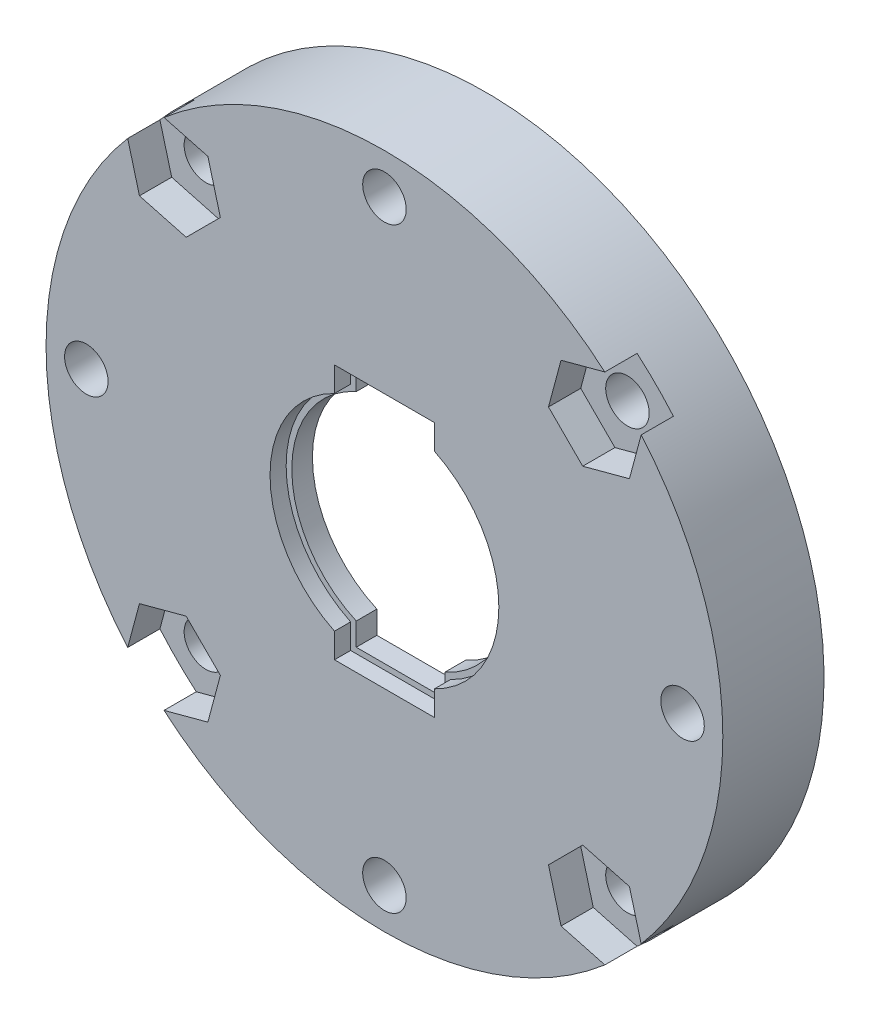
SolidWorks part; units mm, degrees
ref_plane "Front Plane" through (0, 0, 0) normal (0, 0, 1) x (1, 0, 0)
ref_plane "Top Plane" through (0, 0, 0) normal (0, 1, 0) x (1, 0, 0)
ref_plane "Right Plane" through (0, 0, 0) normal (1, 0, 0) x (0, 0, -1)
ref_axis "Z" through (0, 0, -0.1) along (0, 0, 1)
sketch "Sketch3" plane through (0, 0, 0) normal (0, 0, 1) x (1, 0, 0)
  line L0 (-3.1, -6.3875) -> (-3.1, -7.9247)
  line L1 (-3.1, -7.9247) -> (3.1, -7.9247)
  line L2 (3.1, -7.9247) -> (3.1, -6.3875)
  line L3 (3.1, 6.3875) -> (3.1, 7.9244)
  line L4 (3.1, 7.9244) -> (-3.1, 7.9244)
  line L5 (-3.1, 7.9244) -> (-3.1, 6.3875)
  line L132 (3.05, 6.3548) -> (3.05, 6.3561) construction
  line L133 (-3.05, 6.3561) -> (-3.05, 6.3548) construction
  line L134 (3.05, -6.3561) -> (3.05, -6.355) construction
  line L135 (-3.05, -6.355) -> (-3.05, -6.3561) construction
  line L198 (3.05, 6.3548) -> (3.05, 7.8744)
  line L199 (3.05, 7.8744) -> (-3.05, 7.8744)
  line L200 (-3.05, 7.8744) -> (-3.05, 6.3548)
  line L201 (-3.05, 6.3548) -> (-3.4914, 6.1247)
  line L202 (-3.4914, 6.1247) -> (-3.9416, 5.8451)
  line L203 (-3.9416, 5.8451) -> (-4.3696, 5.5325)
  line L204 (-4.3696, 5.5325) -> (-4.7729, 5.1886)
  line L205 (-4.7729, 5.1886) -> (-5.1492, 4.8154)
  line L206 (-5.1492, 4.8154) -> (-5.4964, 4.4149)
  line L207 (-5.4964, 4.4149) -> (-5.8125, 3.9896)
  line L208 (-5.8125, 3.9896) -> (-6.0958, 3.5417)
  line L209 (-6.0958, 3.5417) -> (-6.3446, 3.0737)
  line L210 (-6.3446, 3.0737) -> (-6.5576, 2.5884)
  line L211 (-6.5576, 2.5884) -> (-6.7335, 2.0885)
  line L212 (-6.7335, 2.0885) -> (-6.8714, 1.5768)
  line L213 (-6.8714, 1.5768) -> (-6.9705, 1.0561)
  line L214 (-6.9705, 1.0561) -> (-7.0301, 0.5295)
  line L215 (-7.0301, 0.5295) -> (-7.05, -0.0001)
  line L216 (-7.05, -0.0001) -> (-7.0301, -0.5297)
  line L217 (-7.0301, -0.5297) -> (-6.9705, -1.0563)
  line L218 (-6.9705, -1.0563) -> (-6.8714, -1.577)
  line L219 (-6.8714, -1.577) -> (-6.7335, -2.0887)
  line L220 (-6.7335, -2.0887) -> (-6.5576, -2.5887)
  line L221 (-6.5576, -2.5887) -> (-6.3446, -3.074)
  line L222 (-6.3446, -3.074) -> (-6.0958, -3.5419)
  line L223 (-6.0958, -3.5419) -> (-5.8125, -3.9898)
  line L224 (-5.8125, -3.9898) -> (-5.4964, -4.4152)
  line L225 (-5.4964, -4.4152) -> (-5.1492, -4.8156)
  line L226 (-5.1492, -4.8156) -> (-4.7729, -5.1888)
  line L227 (-4.7729, -5.1888) -> (-4.3696, -5.5327)
  line L228 (-4.3696, -5.5327) -> (-3.9416, -5.8453)
  line L229 (-3.9416, -5.8453) -> (-3.4914, -6.1249)
  line L230 (-3.4914, -6.1249) -> (-3.05, -6.355)
  line L231 (-3.05, -6.355) -> (-3.05, -7.8747)
  line L232 (-3.05, -7.8747) -> (3.05, -7.8747)
  line L233 (3.05, -7.8747) -> (3.05, -6.355)
  line L234 (3.05, -6.355) -> (3.4914, -6.1249)
  line L235 (3.4914, -6.1249) -> (3.9417, -5.8453)
  line L236 (3.9417, -5.8453) -> (4.3696, -5.5327)
  line L237 (4.3696, -5.5327) -> (4.7729, -5.1888)
  line L238 (4.7729, -5.1888) -> (5.1492, -4.8156)
  line L239 (5.1492, -4.8156) -> (5.4964, -4.4152)
  line L240 (5.4964, -4.4152) -> (5.8125, -3.9898)
  line L241 (5.8125, -3.9898) -> (6.0958, -3.5419)
  line L242 (6.0958, -3.5419) -> (6.3447, -3.074)
  line L243 (6.3447, -3.074) -> (6.5576, -2.5887)
  line L244 (6.5576, -2.5887) -> (6.7336, -2.0887)
  line L245 (6.7336, -2.0887) -> (6.8714, -1.577)
  line L246 (6.8714, -1.577) -> (6.9705, -1.0563)
  line L247 (6.9705, -1.0563) -> (7.0301, -0.5297)
  line L248 (7.0301, -0.5297) -> (7.05, -0.0001)
  line L249 (7.05, -0.0001) -> (7.0301, 0.5295)
  line L250 (7.0301, 0.5295) -> (6.9705, 1.0561)
  line L251 (6.9705, 1.0561) -> (6.8714, 1.5768)
  line L252 (6.8714, 1.5768) -> (6.7336, 2.0885)
  line L253 (6.7336, 2.0885) -> (6.5576, 2.5884)
  line L254 (6.5576, 2.5884) -> (6.3447, 3.0737)
  line L255 (6.3447, 3.0737) -> (6.0958, 3.5417)
  line L256 (6.0958, 3.5417) -> (5.8125, 3.9896)
  line L257 (5.8125, 3.9896) -> (5.4964, 4.4149)
  line L258 (5.4964, 4.4149) -> (5.1492, 4.8154)
  line L259 (5.1492, 4.8154) -> (4.7729, 5.1886)
  line L260 (4.7729, 5.1886) -> (4.3696, 5.5325)
  line L261 (4.3696, 5.5325) -> (3.9417, 5.8451)
  line L262 (3.9417, 5.8451) -> (3.4914, 6.1247)
  line L263 (3.4914, 6.1247) -> (3.05, 6.3548)
  line L264 (3.05, 6.3561) -> (3.05, 7.8744) construction
  line L265 (3.05, 7.8744) -> (-3.05, 7.8744) construction
  line L266 (-3.05, 7.8744) -> (-3.05, 6.3561) construction
  line L297 (-3.05, -6.3561) -> (-3.05, -7.8747) construction
  line L298 (-3.05, -7.8747) -> (3.05, -7.8747) construction
  line L299 (3.05, -7.8747) -> (3.05, -6.3561) construction
  arc A1 (-3.05, 6.3561) -> (-3.05, -6.3561) centre (0, 0) ccw construction
  arc A2 (3.05, 6.3561) -> (-3.05, 6.3561) centre (0, 0) ccw construction
  arc A3 (3.05, -6.3561) -> (3.05, 6.3561) centre (0, 0) ccw construction
  arc A4 (-3.05, -6.3561) -> (3.05, -6.3561) centre (0, 0) ccw construction
  circle A5 centre (0, 0) radius 21
  arc A6 (-3.1, 6.3875) -> (-3.1, -6.3875) centre (0, 0) ccw
  arc A7 (3.1, -6.3875) -> (3.1, 6.3875) centre (0, 0) ccw
  dimension "D1" = 14.1
  dimension "D3" = 42
  dimension "D2" = 0.05
  dimension "D4" = 0.05
extrude "Boss-Extrude2" add sketch "Sketch3" against normal blind 1
sketch "Sketch4" plane through (0, 0, -1) normal (0, 0, -1) x (-1, 0, 0)
  line L39 (2.75, 6.1644) -> (2.75, 7.5744)
  line L40 (2.75, 7.5744) -> (-2.75, 7.5744)
  line L41 (-2.75, 7.5744) -> (-2.75, 6.1644)
  line L42 (-2.75, -6.1644) -> (-2.75, -7.5747)
  line L43 (-2.75, -7.5747) -> (2.75, -7.5747)
  line L44 (2.75, -7.5747) -> (2.75, -6.1644)
  circle A14 centre (0, 0) radius 21
  arc A17 (-2.75, 6.1644) -> (-2.75, -6.1644) centre (0, 0) ccw
  arc A18 (2.75, -6.1644) -> (2.75, 6.1644) centre (0, 0) ccw
extrude "Boss-Extrude3" add sketch "Sketch4" along normal blind 5.28
sketch "Sketch5" plane through (0, 0, -6.28) normal (0, 0, -1) x (-1, 0, 0)
  circle A0 centre (0, 0) radius 16.5
  dimension "D1" = 33
extrude "Cut-Extrude1" cut sketch "Sketch5" against normal blind 4
sketch "Sketch6" plane through (0, 0, 0) normal (0, 0, 1) x (1, 0, 0)
  line L0 (0, 0) -> (13.0815, 13.0815) construction
  line L1 (-16.3801, 0) -> (0, 0) construction
  line L3 (13.8585, 15.9814) -> (10.9586, 15.2044)
  line L4 (10.9586, 15.2044) -> (10.1816, 12.3044)
  line L5 (10.1816, 12.3044) -> (12.3044, 10.1816)
  line L6 (12.3044, 10.1816) -> (15.2044, 10.9586)
  line L7 (15.2044, 10.9586) -> (15.9814, 13.8585)
  line L8 (15.9814, 13.8585) -> (13.8585, 15.9814)
  circle A0 centre (13.0815, 13.0815) radius 2.6 construction
  dimension "D3" = 5.2
  dimension "D1" = 135
  dimension "D2" = 18.5
extrude "Cut-Extrude2" cut sketch "Sketch6" against normal blind 2
sketch "Sketch8" plane through (0, 0, 0) normal (0, 0, 1) x (1, 0, 0)
  line L0 (36.6653, 0) -> (49.0214, 0) construction
  line L1 (0, 0) -> (13.0815, 13.0815) construction
  circle A0 centre (0, 0) radius 18.5 construction
  circle A1 centre (13.0815, 13.0815) radius 1.35
  dimension "D1" = 37
  dimension "D3" = 2.7
  dimension "D2" = 135
extrude "Cut-Extrude4" cut sketch "Sketch8" against normal through all
pattern_circular "CirPattern1" count 4 over 360 about axis through (0, 0, -0.1) along (0, 0, 1) of "Cut-Extrude2", "Cut-Extrude4"
ref_plane "Plane4" through (0, 0, 0) normal (-0.7071, 0.7071, 0) x (0, 0, 1)
pattern_circular "CirPattern2" count 8 over 360 about axis through (0, 0, -0.1) along (0, 0, 1) of "Cut-Extrude4"
